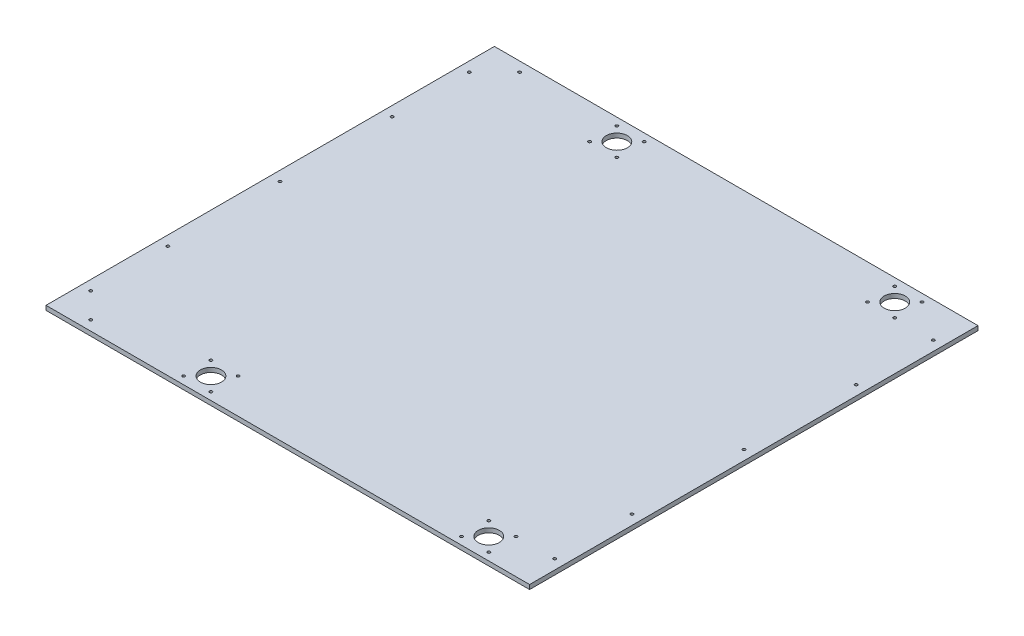
SolidWorks part; units mm, degrees
ref_plane "Front Plane" through (0, 0, 0) normal (0, 0, 1) x (1, 0, 0)
ref_plane "Top Plane" through (0, 0, 0) normal (0, 1, 0) x (1, 0, 0)
ref_plane "Right Plane" through (0, 0, 0) normal (1, 0, 0) x (0, 0, -1)
sketch "Sketch1" plane through (0, 0, 0) normal (1, 0, 0) x (0, 0, -1)
  line L0 (0, 0) -> (-510, 0)
  line L1 (-510, 0) -> (-510, 5)
  line L2 (-510, 5) -> (0, 5)
  line L6 (0, 5) -> (0, 0)
  dimension "D1" = 510
  dimension "D2" = 5
extrude "Boss-Extrude1" add sketch "Sketch1" along normal blind 550
sketch "BotthomHoles-Sketch2" plane through (0, 5, 0) normal (0, 1, 0) x (1, 0, 0)
  line L0 (550, -3.175) -> (0, -3.175) construction
  line L2 (550, 0) -> (550, -510) construction
  line L3 (550, 0) -> (0, 0) construction
  line L4 (550, -510) -> (0, -510) construction
  line L7 (0, 0) -> (0, -510) construction
  line L8 (550, 0) -> (550, -510) construction
  circle A0 centre (479.425, -24.175) radius 12
  circle A2 centre (463.925, -8.675) radius 1.5875
  circle A3 centre (494.925, -8.675) radius 1.5875
  circle A6 centre (463.925, -39.675) radius 1.5875
  circle A7 centre (494.925, -39.675) radius 1.5875
  circle A8 centre (39.6875, -11.1125) radius 1.5875
  circle A10 centre (178.925, -39.675) radius 1.5875
  circle A11 centre (147.925, -39.675) radius 1.5875
  circle A12 centre (178.925, -8.675) radius 1.5875
  circle A13 centre (147.925, -8.675) radius 1.5875
  circle A14 centre (163.425, -24.175) radius 12
  circle A15 centre (39.6875, -498.8875) radius 1.5875
  circle A16 centre (147.925, -501.325) radius 1.5875
  circle A17 centre (178.925, -501.325) radius 1.5875
  circle A18 centre (147.925, -470.325) radius 1.5875
  circle A19 centre (178.925, -470.325) radius 1.5875
  circle A20 centre (463.925, -470.325) radius 1.5875
  circle A21 centre (463.925, -501.325) radius 1.5875
  circle A22 centre (494.925, -470.325) radius 1.5875
  circle A23 centre (494.925, -501.325) radius 1.5875
  circle A25 centre (163.425, -485.825) radius 12
  circle A26 centre (479.425, -485.825) radius 12
  circle A27 centre (11.1125, -39.6875) radius 1.5875
  circle A28 centre (11.1125, -127.5) radius 1.5875
  circle A29 centre (11.1125, -255) radius 1.5875
  circle A30 centre (11.1125, -382.5) radius 1.5875
  circle A31 centre (11.1125, -470.3125) radius 1.5875
  circle A32 centre (538.8875, -470.3125) radius 1.5875
  circle A33 centre (538.8875, -382.5) radius 1.5875
  circle A34 centre (538.8875, -255) radius 1.5875
  circle A35 centre (538.8875, -127.5) radius 1.5875
  circle A36 centre (538.8875, -39.6875) radius 1.5875
  dimension "D9" = 3.175
  dimension "D10" = 24
  dimension "D13" = 3.175
  dimension "D29" = 3.175
  dimension "D2" = 8.675
  dimension "D5" = 15.5
  dimension "D6" = 31
  dimension "D7" = 15.5
  dimension "D8" = 31
  dimension "D11" = 21
  dimension "D12" = 39.6875
  dimension "D15" = 31
  dimension "D16" = 15.5
  dimension "D17" = 316
  dimension "D3" = 70.575
  dimension "D4" = 11.1125
  dimension "D18" = 8.675
  dimension "D19" = 15.5
  dimension "D20" = 31
  dimension "D21" = 11.1125
  dimension "D22" = 39.6875
  dimension "D23" = 39.6875
  dimension "D24" = 127.5
  dimension "D25" = 127.5
  dimension "D26" = 127.5
  dimension "D27" = 11.1125
  dimension "D28" = 11.1125
extrude "BottomHoles-Cut-Extrude1" cut sketch "BotthomHoles-Sketch2" against normal through all
equation "\"LowerRailWidth\"= 2.00in"
equation "\"RailThickness\"= .125in'Spec"
equation "\"StepperHoleDiameter\"= 24mm"
equation "\"StepperMountingHoleDiameter\"= 3.175mm"
equation "\"SideRailLength\"= 550mm"
equation "\"StepperMountingHoleDistance\"= 31mm'Spec"
equation "\"StepperMountingHoleOffsetFromLeftOrRightSide\"= \"StepperMountingHoleOffsetFromItsSide\" + \"RailThickness\""
equation "\"HoleOffsetFromEdge\"= \"RailThickness\" * 2.5"
equation "\"HoleOffsetFromSide\"= \"RailThickness\" * 3.5"
equation "\"StepperMountingHoleOffsetFromItsSide\"= 5.5mm'Spec"
equation "\"FasteningHoleDiameter\"= .125in"
equation "\"D2@BotthomHoles-Sketch2\" = \"StepperMountingHoleOffsetFromLeftOrRightSide\""
equation "\"D5@BotthomHoles-Sketch2\" = \"StepperMountingHoleDistance\" / 2"
equation "\"D6@BotthomHoles-Sketch2\" = \"StepperMountingHoleDistance\""
equation "\"D7@BotthomHoles-Sketch2\" = \"StepperMountingHoleDistance\" / 2"
equation "\"D8@BotthomHoles-Sketch2\" = \"StepperMountingHoleDistance\""
equation "\"D9@BotthomHoles-Sketch2\" = \"StepperMountingHoleDiameter\""
equation "\"D10@BotthomHoles-Sketch2\" = \"StepperHoleDiameter\""
equation "\"D1@Boss-Extrude1\"=\"SideRailLength\""
equation "\"BedOverlap\"= 20mm"
equation "\"BedThirdSize\"= 70mm"
equation "\"BedInnerSquareWidth\"= \"BedThirdSize\" * 3'Equals 210"
equation "\"BedInnerSquareLength\"= \"BedInnerSquareWidth\""
equation "\"BedLWidth\"= \"BedThirdSize\" + \"BedOverlap\"'Equals 90"
equation "\"BedLength\"= \"BedInnerSquareLength\" + \"BedLWidth\" * 2 - \"BedOverlap\" * 2 + \"BedIncreasedByLength\"'Equals 350"
equation "\"DistanceBetweenFrontToBackStepperHoles\"= \"BedLength\" - \"DistanceFromBedFrontToFirstLeftStepperHole\"'Equals 316"
equation "\"DistanceFromBedFrontToFirstLeftStepperHole\"= \"LeadScrewNutPadSize\" + 10mm'Equals 34"
equation "\"DistanceFromFrontSideToBedFront\"= \"RailThickness\" + \"BeltTensionerDepth\" + 10mm'Equals 36.575"
equation "\"20TGT2PulleyDiameter\"= 17.9mm'Spec"
equation "\"BeltTensionerBackWallThickness\"= 4mm"
equation "\"BeltTensionerSpaceBetweenPulleyAndWall\"= 1.5mm"
equation "\"BeltTensionerInnerDepth\"= \"20TGT2PulleyDiameter\" + \"BeltTensionerSpaceBetweenPulleyAndWall\""
equation "\"BeltTensionerDepth\"= \"BeltTensionerBackWallThickness\" + \"BeltTensionerInnerDepth\"'Equals 23.4"
equation "\"BedIncreasedByLength\"= 0mm"
equation "\"LowerCornerBlockWidth\"= \"LowerRailWidth\" - \"RailThickness\" * 2'Room for left front stepper"
equation "\"D12@BotthomHoles-Sketch2\"=\"CornerEnclosureOffset\""
equation "\"D13@BotthomHoles-Sketch2\"=\"FasteningHoleDiameter\""
equation "\"CornerEnclosureOffset\"= \"LowerCornerBlockWidth\" - \"HoleOffsetFromEdge\" + \"RailThickness\""
equation "\"LowerCornerBlockY1FromSide\"= \"HoleOffsetFromSide\""
equation "\"D15@BotthomHoles-Sketch2\"=\"StepperMountingHoleDistance\""
equation "\"D16@BotthomHoles-Sketch2\"=\"StepperMountingHoleDistance\"/2"
equation "\"D17@BotthomHoles-Sketch2\"=\"DistanceBetweenFrontToBackStepperHoles\""
equation "\"DistanceFromFrontSideToFirstLeftStepperHole\"= \"DistanceFromFrontSideToBedFront\" + \"DistanceFromBedFrontToFirstLeftStepperHole\"'Equals 70.575"
equation "\"LeadScrewNutMountingHoleFlangeDiameter\"= 22mm'Spec"
equation "\"LeadScrewNutPadSize\"= \"LeadScrewNutMountingHoleFlangeDiameter\" + 2mm'Equals 24"
equation "\"D3@BotthomHoles-Sketch2\"=\"DistanceFromFrontSideToFirstLeftStepperHole\""
equation "\"LowerEnclosureThickness\"= 5.0mm"
equation "\"FrontBackRailLength\"= 510mm"
equation "\"D4@BotthomHoles-Sketch2\"=\"LowerCornerBlockY1FromSide\""
equation "\"D1@Sketch1\"=\"FrontBackRailLength\""
equation "\"D18@BotthomHoles-Sketch2\"=\"StepperMountingHoleOffsetFromLeftOrRightSide\""
equation "\"D19@BotthomHoles-Sketch2\"=\"StepperMountingHoleDistance\"/2"
equation "\"D20@BotthomHoles-Sketch2\"=\"StepperMountingHoleDistance\""
equation "\"D21@BotthomHoles-Sketch2\"=\"LowerCornerBlockY1FromSide\""
equation "\"D22@BotthomHoles-Sketch2\"=\"CornerEnclosureOffset\""
equation "\"D23@BotthomHoles-Sketch2\"=\"CornerEnclosureOffset\""
equation "\"FrontOrBackEnclosureOffsets\"= \"FrontBackRailLength\" / 4"
equation "\"D24@BotthomHoles-Sketch2\"=\"FrontOrBackEnclosureOffsets\""
equation "\"D25@BotthomHoles-Sketch2\"=\"FrontOrBackEnclosureOffsets\""
equation "\"D26@BotthomHoles-Sketch2\"=\"FrontOrBackEnclosureOffsets\""
equation "\"D27@BotthomHoles-Sketch2\"=\"LowerCornerBlockY1FromSide\""
equation "\"D28@BotthomHoles-Sketch2\"=\"LowerCornerBlockY1FromSide\""
equation "\"D29@BotthomHoles-Sketch2\"=\"FasteningHoleDiameter\""
equation "\"D2@Sketch1\"=\"LowerEnclosureThickness\""
